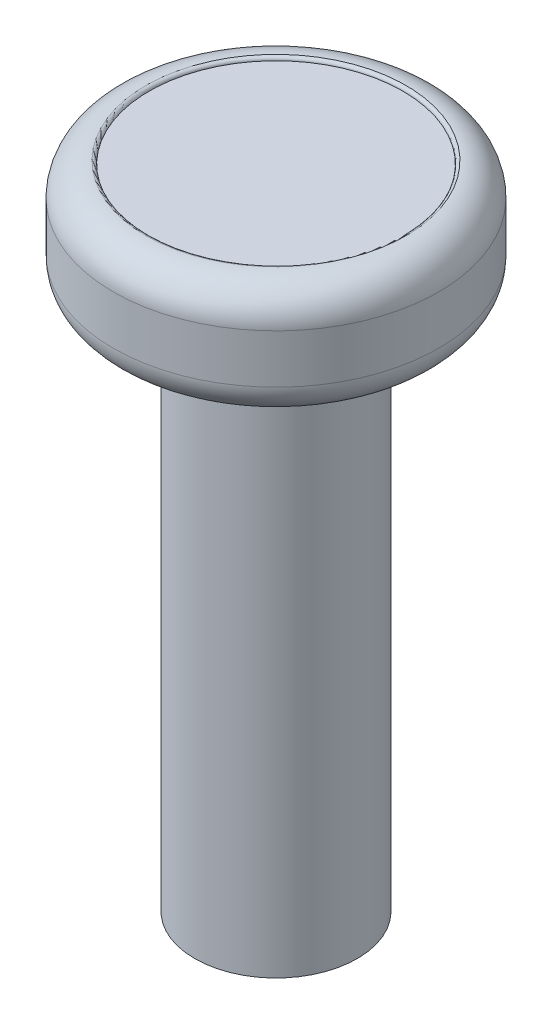
SolidWorks part; units mm, degrees
ref_plane "Front Plane" through (0, 0, 0) normal (0, 0, 1) x (1, 0, 0)
ref_plane "Top Plane" through (0, 0, 0) normal (0, 1, 0) x (1, 0, 0)
ref_plane "Right Plane" through (0, 0, 0) normal (1, 0, 0) x (0, 0, -1)
sketch "Sketch2" plane through (0, 0, 0) normal (0, 1, 0) x (1, 0, 0)
  line L1 (-1, 0.625) -> (1, 0.625)
  line L2 (-1, 0.625) -> (-1, -0.625)
  line L3 (-1, -0.625) -> (1, -0.625)
  line L4 (1, 0.625) -> (1, -0.625)
  line L5 (-1, 0.625) -> (1, -0.625) construction
  line L6 (-1, -0.625) -> (1, 0.625) construction
  circle A0 centre (0, 0) radius 2.5
  dimension "D1" = 5
  dimension "D2" = 1.25
  dimension "D3" = 2
extrude "Boss-Extrude1" add sketch "Sketch2" along normal mid plane 20
fillet "Fillet1" radius 1 1 edges at (0, 10, 2.5)
sketch "Sketch3" plane through (0, 10, 0) normal (0, 1, 0) x (1, 0, 0)
  line L0 (1, -0.625) -> (1, 0.625) construction
  line L1 (-1, -0.625) -> (1, -0.625) construction
  line L2 (-1, 0.625) -> (-1, -0.625) construction
  line L3 (1, 0.625) -> (-1, 0.625) construction
  line L4 (1, -0.625) -> (1, 0.625)
  line L5 (-1, -0.625) -> (1, -0.625)
  line L6 (-1, 0.625) -> (-1, -0.625)
  line L7 (1, 0.625) -> (-1, 0.625)
extrude "Boss-Extrude5" add sketch "Sketch3" against normal blind 16
sketch "Sketch4" plane through (0, 10, 0) normal (0, 1, 0) x (1, 0, 0)
  circle A0 centre (0, 0) radius 5
  circle A1 centre (0, 0) radius 4
  circle A2 centre (0, 0) radius 3.9
  dimension "D1" = 10
  dimension "D2" = 8
  dimension "D3" = 0.1
extrude "Thumb Stick" add sketch "Sketch4" against normal blind 3.5 contours A0
fillet "Fillet2" radius 1 1 edges at (0, 6.5, 5)
fillet "Fillet3" radius 1 1 edges at (0, 10, 5)
extrude "Cut-Extrude1" cut sketch "Sketch4<4>" against normal blind 0.1 contours A2
sketch "Sketch4<4>" plane through (0, 10, 0) normal (0, 1, 0) x (1, 0, 0) same geometry as "Sketch4"
fillet "Fillet5" radius 0.1 1 edges at (0, 10, 3.9)
